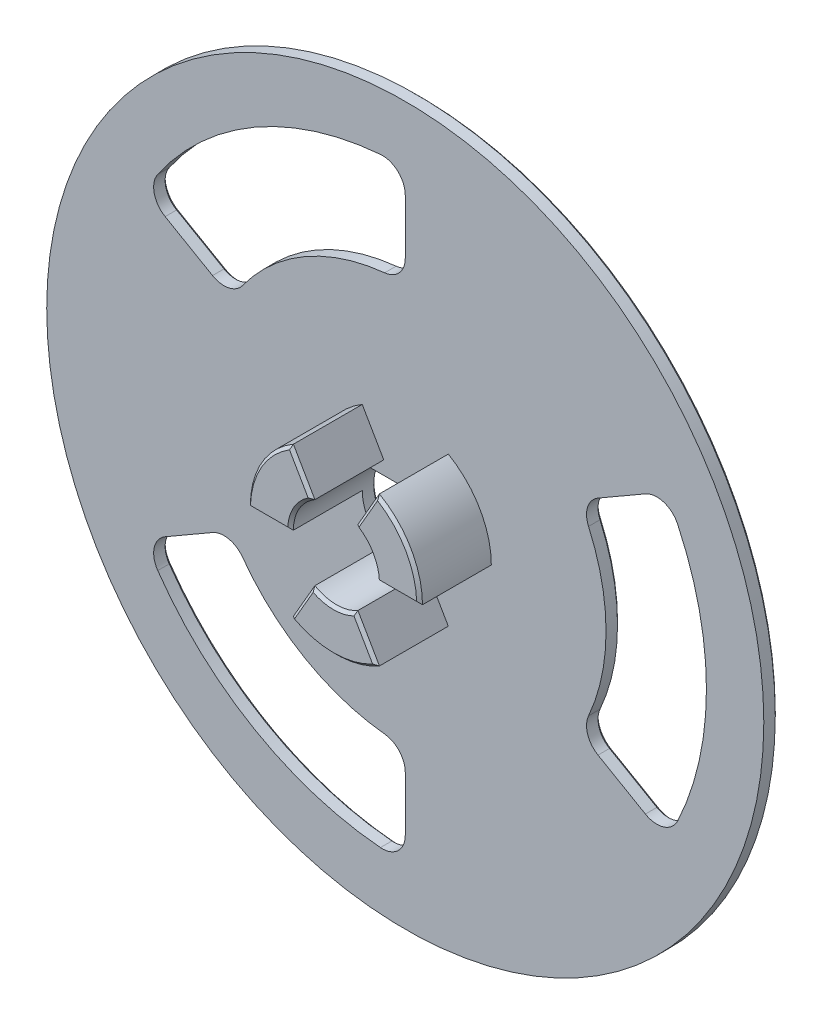
SolidWorks part; units mm, degrees
note: The reader was unsure of these and kept them because the rebuilt part matched: shared geometry of "草图1<5>".
material "ABS"
ref_plane "前视基准面" through (0, 0, 0) normal (0, 0, 1) x (1, 0, 0)
ref_plane "上视基准面" through (0, 0, 0) normal (0, 1, 0) x (1, 0, 0)
ref_plane "右视基准面" through (0, 0, 0) normal (1, 0, 0) x (0, 0, -1)
sketch "草图1" plane through (0, 0, 0) normal (0, 0, 1) x (1, 0, 0)
  line L0 (-2.5, 1.6583) -> (2.5, 1.6583)
  line L1 (-7.8785, 1.3892) -> (-5.9088, 1.0419)
  line L2 (0, 0) -> (-8, 0) construction
  line L3 (-7.5175, 2.7362) -> (-5.6382, 2.0521)
  line L4 (3, 0) -> (6, 0)
  line L5 (1.5, -2.5981) -> (3, -5.1962)
  line L6 (-1.5, -2.5981) -> (-3, -5.1962)
  line L7 (-3, 0) -> (-6, 0)
  line L8 (-1.5, 2.5981) -> (-3, 5.1962)
  line L9 (1.5, 2.5981) -> (3, 5.1962)
  line L10 (0, -14) -> (0, -21)
  line L11 (-12.1244, -7) -> (-18.1865, -10.5)
  line L12 (-12.1244, 7) -> (-18.1865, 10.5)
  line L13 (0, 14) -> (0, 21)
  line L14 (12.1244, 7) -> (18.1865, 10.5)
  line L15 (12.1244, -7) -> (18.1865, -10.5)
  circle A0 centre (0, 0) radius 3
  circle A2 centre (0, 0) radius 25
  arc A3 (3, 5.1962) -> (-3, 5.1962) centre (0, 0) ccw
  circle A4 centre (0, 0) radius 8
  arc A5 (0, 14) -> (-12.1244, 7) centre (0, 0) ccw
  arc A6 (0, 21) -> (-18.1865, 10.5) centre (0, 0) ccw
  arc A7 (18.1865, -10.5) -> (18.1865, 10.5) centre (0, 0) ccw
  arc A8 (12.1244, -7) -> (12.1244, 7) centre (0, 0) ccw
  arc A9 (-18.1865, -10.5) -> (0, -21) centre (0, 0) ccw
  arc A10 (-12.1244, -7) -> (0, -14) centre (0, 0) ccw
  arc A11 (3, -5.1962) -> (6, 0) centre (0, 0) ccw
  arc A12 (-5.6382, 2.0521) -> (-5.9088, 1.0419) centre (0, 0) ccw
  arc A13 (-6, 0) -> (-3, -5.1962) centre (0, 0) ccw
  circle A15 centre (0, 0) radius 6
  point P28 (0, 0)
  point P30 (0, 0)
  point P42 (0, 0)
  dimension "D1" = 6
  dimension "D3" = 6
  dimension "D4" = 50
  dimension "D7" = 16
  dimension "D8" = 12
  dimension "D10" = 28
  dimension "D11" = 42
  dimension "D2" = 5
  dimension "D5" = 10
  dimension "D6" = 20
  dimension "D9" = 6
extrude "凸台-拉伸1" add sketch "草图1" against normal blind 1
fillet "圆角1" radius 1.6 12 edges at (-18.1865, -10.5, -0.5) (-12.1244, -7, -0.5) (0, -14, -0.5) (0, -21, -0.5) (18.1865, -10.5, -0.5) (18.1865, 10.5, -0.5) (12.1244, 7, -0.5) (12.1244, -7, -0.5) (-18.1865, 10.5, -0.5) (-12.1244, 7, -0.5) (0, 14, -0.5) (0, 21, -0.5)
extrude "凸台-拉伸3" add sketch "草图1<5>" along normal blind 5
sketch "草图1<5>" plane through (0, 0, 0) normal (0, 0, 1) x (1, 0, 0) same geometry as "草图1"
chamfer "倒角3" distance 0.2 angle 45 39 edges at (-0.412, -14.4459, -1) (0, -17.4258, -1) (-0.5163, -20.511, -1) (-10.5, -18.1865, -1) (-17.5049, -10.7026, -1) (-15.0912, -8.7129, -1) (-12.3045, -7.5798, -1) (-7, -12.1244, -1) (12.7166, 6.8661, -1) (15.0912, 8.7129, -1) (18.0212, 9.8084, -1) (21, 0, -1) (18.0212, -9.8084, -1) (15.0912, -8.7129, -1) (12.7166, -6.8661, -1) (14, 0, -1) (25, 0, -1) (-0.412, 14.4459, -1) (-7, 12.1244, -1) (-12.3045, 7.5798, -1) (-15.0912, 8.7129, -1) (-17.5049, 10.7026, -1) (-10.5, 18.1865, -1) (-0.5163, 20.511, -1) (0, 17.4258, -1) (0, 1.6583, -1) (0, -3, -1) (0, -3, 5) (2.25, -3.8971, 5) (0, -6, 5) (-2.25, -3.8971, 5) (2.5981, 1.5, 5) (2.25, 3.8971, 5) (5.1962, 3, 5) (4.5, 0, 5) (-2.5981, 1.5, 5) (-4.5, 0, 5) (-5.1962, 3, 5) (-2.25, 3.8971, 5)
